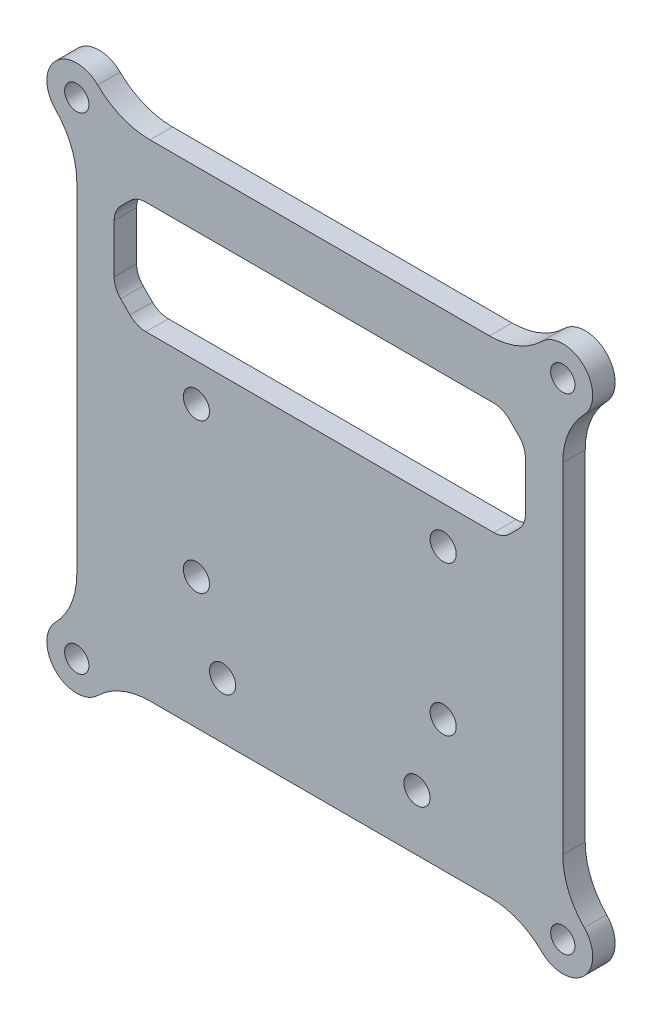
SolidWorks part; units mm, degrees
material "ABS"
ref_plane "Спереди" through (0, 0, 0) normal (0, 0, 1) x (1, 0, 0)
ref_plane "Сверху" through (0, 0, 0) normal (0, 1, 0) x (1, 0, 0)
ref_plane "Справа" through (0, 0, 0) normal (1, 0, 0) x (0, 0, -1)
sketch "Эскиз1" plane through (0, 0, 0) normal (0, 0, 1) x (1, 0, 0)
  line L1 (-32.5, -32.5) -> (32.5, -32.5)
  line L2 (-32.5, -32.5) -> (-32.5, 32.5)
  line L3 (-32.5, 32.5) -> (32.5, 32.5)
  line L4 (32.5, -32.5) -> (32.5, 32.5)
  line L5 (-32.5, -32.5) -> (32.5, 32.5) construction
  line L6 (-32.5, 32.5) -> (32.5, -32.5) construction
  circle A0 centre (-32.5, 32.5) radius 1.625
  arc A1 (-28.5, 32.5) -> (-32.5, 28.5) centre (-32.5, 32.5) ccw
  circle A2 centre (32.5, 32.5) radius 1.625
  arc A3 (32.5, 28.5) -> (28.5, 32.5) centre (32.5, 32.5) ccw
  circle A4 centre (32.5, -32.5) radius 1.625
  arc A5 (28.5, -32.5) -> (32.5, -28.5) centre (32.5, -32.5) ccw
  circle A6 centre (-32.5, -32.5) radius 1.625
  arc A7 (-32.5, -28.5) -> (-28.5, -32.5) centre (-32.5, -32.5) ccw
  point P0 (0, 0)
  point P20 (0, 0)
  dimension "D2" = 3.25
  dimension "D3" = 8
  dimension "D1" = 65
  dimension "D4" = 4
extrude "Бобышка-Вытянуть1" add sketch "Эскиз1" along normal blind 3 contours A6 L1 A4 L4 A2 L3 A0 L2 | L3 A1 L2 A0 | L4 A3 L3 A2 | L1 A5 L4 A4 | L2 A7 L1 A6 region at (0, 0, 0) region at (-29.6875, -32.6131, 0) region at (29.6875, -32.6131, 0) region at (-35.2484, 35.2484, 0) region at (32.6131, 29.6875, 0)
fillet "Скругление1" radius 10 8 edges at (-28.5, -32.5, 1.5) (-32.5, -28.5, 1.5) (-28.5, 32.5, 1.5) (-32.5, 28.5, 1.5) (28.5, 32.5, 1.5) (32.5, 28.5, 1.5) (32.5, -28.5, 1.5) (28.5, -32.5, 1.5)
sketch "Эскиз2" plane through (0, 0, 3) normal (0, 0, 1) x (1, 0, 0)
  line L0 (0, 32.5) -> (0, -32.5) construction
  line L1 (-22.702, 32.5) -> (22.702, 32.5) construction
  line L2 (-22.702, -32.5) -> (22.702, -32.5) construction
  line L3 (-15.6432, -25) -> (20.4381, -25) construction
  circle A0 centre (-13, -25) radius 1.75
  circle A1 centre (13, -25) radius 1.75
  dimension "D1" = 3.5
  dimension "D2" = 13
  dimension "D3" = 7.5
sketch "Эскиз3" plane through (0, 0, 3) normal (0, 0, 1) x (1, 0, 0)
  circle A0 centre (0, 0) radius 50
  dimension "D1" = 100
extrude "Вырез-Вытянуть1" cut sketch "Эскиз2" against normal blind 10
sketch "Эскиз4" plane through (0, 0, 3) normal (0, 0, 1) x (1, 0, 0)
  line L0 (0, -32.5) -> (0, 32.5) construction
  line L1 (-22.702, -32.5) -> (22.702, -32.5) construction
  line L2 (-22.702, 32.5) -> (22.702, 32.5) construction
  line L3 (-22.6055, -15) -> (24.9146, -15) construction
  circle A0 centre (-16.5, -15) radius 1.75
  circle A1 centre (16.5, -15) radius 1.75
  dimension "D1" = 3.5
  dimension "D2" = 16.5
  dimension "D3" = 17.5
extrude "Вырез-Вытянуть2" cut sketch "Эскиз4" against normal blind 10
sketch "Эскиз5" plane through (0, 0, 3) normal (0, 0, 1) x (1, 0, 0)
  line L0 (-32.5, 5) -> (32.5, 5) construction
  line L1 (-32.5, -22.702) -> (-32.5, 22.702) construction
  line L2 (32.5, -22.702) -> (32.5, 22.702) construction
  line L3 (0, -32.5) -> (0, 32.5) construction
  line L4 (-22.702, -32.5) -> (22.702, -32.5) construction
  line L5 (-22.702, 32.5) -> (22.702, 32.5) construction
  circle A0 centre (-16.5, 5) radius 1.75
  circle A1 centre (16.5, 5) radius 1.75
  dimension "D1" = 3.5
  dimension "D2" = 16.5
  dimension "D3" = 37.5
extrude "Вырез-Вытянуть3" cut sketch "Эскиз5" against normal blind 10
sketch "Эскиз7" plane through (0, 0, 3) normal (0, 0, 1) x (1, 0, 0)
  line L0 (-32.5, -22.702) -> (-32.5, 22.702) construction
  line L1 (-24.5, 25) -> (24.5, 25)
  line L2 (-27.5, 22) -> (-27.5, 13)
  line L3 (-24.5, 10) -> (24.5, 10)
  line L4 (27.5, 22) -> (27.5, 13)
  line L5 (-27.5, 25) -> (27.5, 10) construction
  line L6 (-27.5, 10) -> (27.5, 25) construction
  line L7 (32.5, -22.702) -> (32.5, 22.702) construction
  line L8 (-27.5, 22) -> (-24.5, 25)
  line L9 (-27.5, 13) -> (-24.5, 10)
  line L10 (24.5, 10) -> (27.5, 13)
  line L11 (24.5, 25) -> (27.5, 22)
  point P0 (0, 17.5)
  dimension "D1" = 5
  dimension "D2" = 5
  dimension "D3" = 5
  dimension "D4" = 15
extrude "Вырез-Вытянуть4" cut sketch "Эскиз7" against normal blind 10
fillet "Скругление2" radius 3 8 edges at (27.5, 22, 1.5) (24.5, 25, 1.5) (27.5, 13, 1.5) (24.5, 10, 1.5) (-24.5, 10, 1.5) (-27.5, 13, 1.5) (-24.5, 25, 1.5) (-27.5, 22, 1.5)
